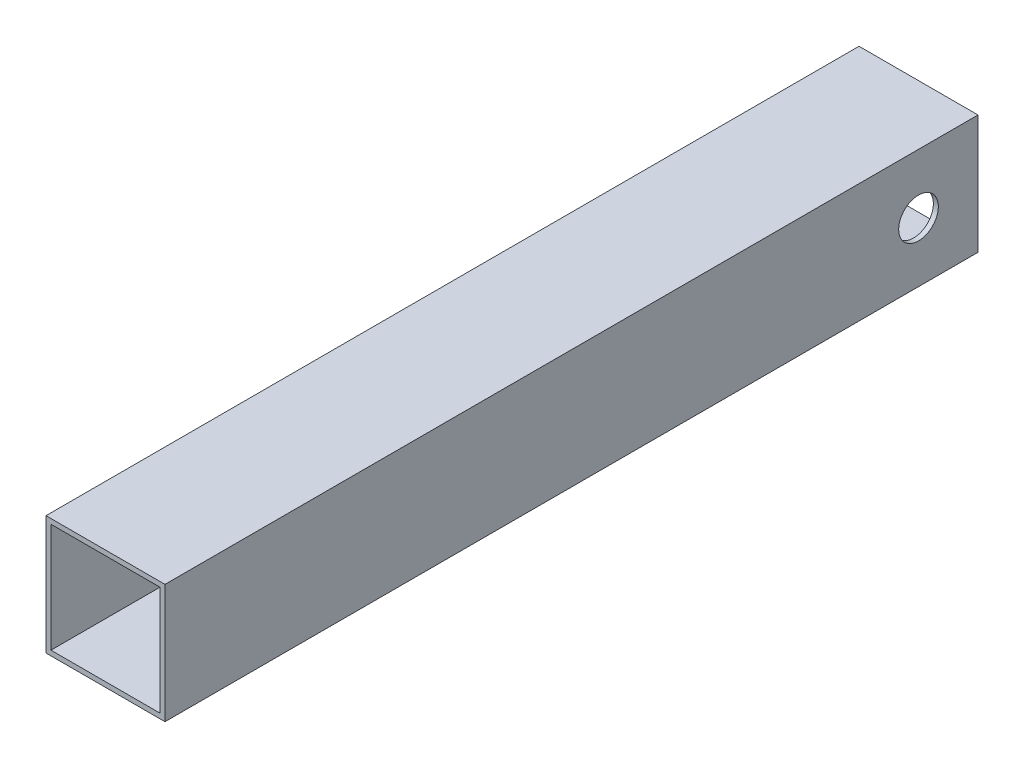
SolidWorks part; units mm, degrees
material "Plain Carbon Steel"
ref_plane "Front Plane" through (0, 0, 0) normal (0, 0, 1) x (1, 0, 0)
ref_plane "Top Plane" through (0, 0, 0) normal (0, 1, 0) x (1, 0, 0)
ref_plane "Right Plane" through (0, 0, 0) normal (1, 0, 0) x (0, 0, -1)
sketch "Sketch2" plane through (0, 0, 0) normal (0, 0, 1) x (1, 0, 0)
  line L0 (0, 19.05) -> (1.5875, 19.05) construction
  line L1 (0, 0) -> (38.1, 0)
  line L2 (0, 0) -> (0, 38.1)
  line L3 (0, 38.1) -> (38.1, 38.1)
  line L4 (38.1, 0) -> (38.1, 38.1)
  line L5 (1.5875, 1.5875) -> (36.5125, 1.5875)
  line L6 (1.5875, 1.5875) -> (1.5875, 36.5125)
  line L7 (1.5875, 36.5125) -> (36.5125, 36.5125)
  line L8 (36.5125, 1.5875) -> (36.5125, 36.5125)
  line L9 (19.05, 36.5125) -> (19.05, 38.1) construction
  line L10 (36.5125, 19.05) -> (38.1, 19.05) construction
  line L11 (19.05, 0) -> (19.05, 1.5875) construction
  dimension "D1" = 38.1
  dimension "D2" = 1.5875
  dimension "D3" = 38.1
extrude "Boss-Extrude1" add sketch "Sketch2" along normal blind 260.35
hole_wizard "1/2 (0.5) Diameter Hole1" positions "Sketch4" profile "Sketch3" hole size "1/2" standard "ANSI Inch" end condition through all
sketch "Sketch4" plane through (0, 0, 0) normal (-1, 0, 0) x (0, 0, 1)
  line L0 (0, 19.05) -> (19.05, 19.05) construction
  line L1 (0, 38.1) -> (0, 0) construction
  point P0 (19.05, 19.05)
  dimension "D1" = 19.05
sketch "Sketch3" plane through (0, 19.05, 19.05) normal (0, 1, 0) x (0, 0, 1)
  line L0 (0, 0) -> (0, 38.1)
  line L1 (0, 38.1) -> (6.35, 38.1)
  line L2 (6.35, 38.1) -> (6.35, 0)
  line L5 (6.35, 0) -> (0, 0)
  line L11 (0, -6.35) -> (0, 107.95) construction
  dimension "Thru Hole Dia." = 12.7
  dimension "Thru Hole Depth" = 38.1
